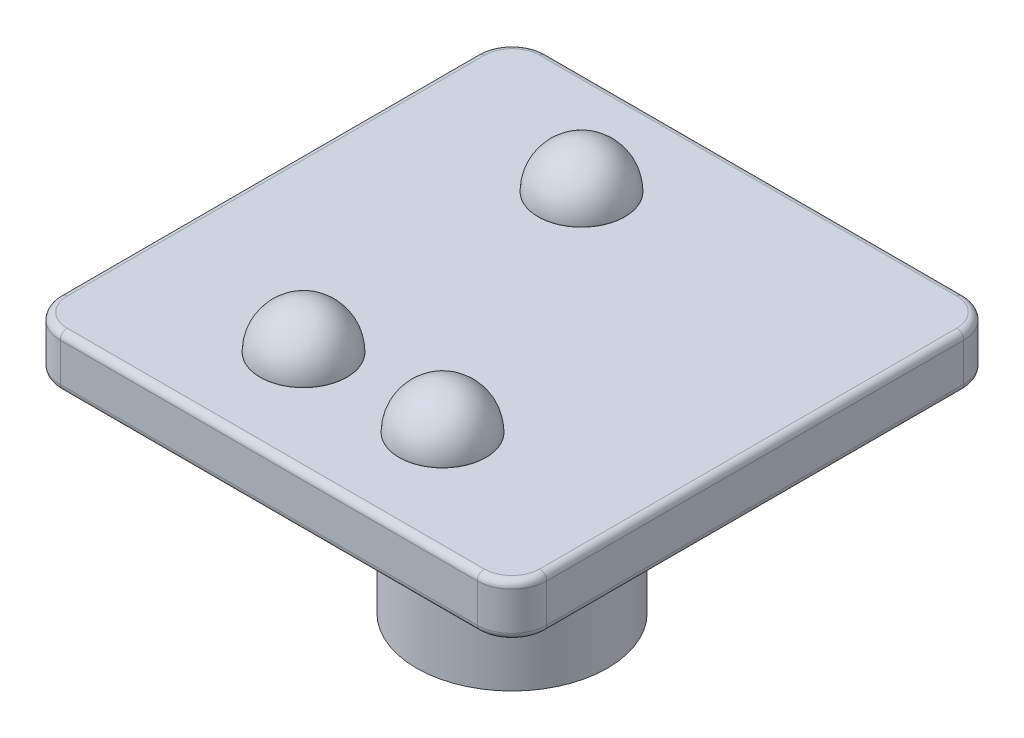
SolidWorks part; units mm, degrees
ref_plane "Front Plane" through (0, 0, 0) normal (0, 0, 1) x (1, 0, 0)
ref_plane "Top Plane" through (0, 0, 0) normal (0, 1, 0) x (1, 0, 0)
ref_plane "Right Plane" through (0, 0, 0) normal (1, 0, 0) x (0, 0, -1)
sketch "Sketch1" plane through (0, 0, 0) normal (0, 1, 0) x (1, 0, 0)
  line L1 (-7.3247, 4.3967) -> (4.6753, 4.3967)
  line L2 (-8.3247, 3.3967) -> (-8.3247, -8.6033)
  line L3 (-7.3247, -9.6033) -> (4.6753, -9.6033)
  line L4 (5.6753, 3.3967) -> (5.6753, -8.6033)
  arc A0 (-8.3247, -8.6033) -> (-7.3247, -9.6033) centre (-7.3247, -8.6033) ccw
  arc A1 (4.6753, -9.6033) -> (5.6753, -8.6033) centre (4.6753, -8.6033) ccw
  arc A2 (4.6753, 4.3967) -> (5.6753, 3.3967) centre (4.6753, 3.3967) cw
  arc A3 (-7.3247, 4.3967) -> (-8.3247, 3.3967) centre (-7.3247, 3.3967) ccw
  point P8 (5.6753, -9.6033)
  point P11 (5.6753, 4.3967)
  point P14 (-8.3247, 4.3967)
  dimension "D3" = 1
  dimension "D1" = 14
  dimension "D2" = 14
extrude "Boss-Extrude1" add sketch "Sketch1" along normal blind 1.5
sketch "Sketch2" plane through (0, 0, 0) normal (0, -1, 0) x (1, 0, 0)
  line L0 (-7.3247, 9.6033) -> (4.6753, 9.6033) construction
  line L1 (5.6753, 8.6033) -> (5.6753, -3.3967) construction
  line L2 (-1.3247, -4.3967) -> (-1.3247, 9.6033) construction
  line L3 (-8.3247, 2.6033) -> (5.6753, 2.6033) construction
  line L4 (-8.3247, -3.3967) -> (-8.3247, 8.6033) construction
  circle A0 centre (-1.3247, 2.6033) radius 2.75
  dimension "D1" = 7
  dimension "D2" = 7
extrude "Boss-Extrude2" add sketch "Sketch2" along normal blind 6
sketch "Sketch3" plane through (0, -6, 0) normal (0, -1, 0) x (1, 0, 0)
  line L0 (-1.3247, 5.3533) -> (-1.3247, -0.1467) construction
  line L1 (-3.3247, 3.1533) -> (0.6753, 3.1533)
  line L2 (-3.3247, 3.1533) -> (-3.3247, 2.0533)
  line L3 (-3.3247, 2.0533) -> (0.6753, 2.0533)
  line L4 (0.6753, 3.1533) -> (0.6753, 2.0533)
  line L5 (-1.8747, 4.6033) -> (-0.7747, 4.6033)
  line L6 (-1.8747, 4.6033) -> (-1.8747, 0.6033)
  line L7 (-1.8747, 0.6033) -> (-0.7747, 0.6033)
  line L8 (-0.7747, 4.6033) -> (-0.7747, 0.6033)
  line L9 (-4.0747, 2.6033) -> (1.4253, 2.6033) construction
  circle A3 centre (-1.3247, 2.6033) radius 2.75 construction
  circle A4 centre (-1.3247, 2.6033) radius 2.75 construction
  dimension "D7" = 0.55
  dimension "D1" = 4
  dimension "D2" = 1.1
  dimension "D3" = 1.1
  dimension "D4" = 4
  dimension "D8" = 0.55
extrude "Cut-Extrude1" cut sketch "Sketch3" against normal blind 6 contours L8 L5 L6 L1 | L1 L8 L3 L4 | L8 L1 L6 L3 | L6 L1 L2 L3 | L8 L3 L6 L7 region at (-2.5997, -6, 2.6033) region at (-1.3247, -6, 3.8783) region at (-1.3247, -6, 2.6033) region at (-0.0497, -6, 2.6033) region at (-1.3247, -6, 1.3283)
chamfer "Chamfer1" distance 0.3 angle 45 12 edges at (-1.3247, -6, 0.6033) (-1.8747, -6, 1.3283) (-2.5997, -6, 2.0533) (-3.3247, -6, 2.6033) (-2.5997, -6, 3.1533) (-0.7747, -6, 1.3283) (-0.0497, -6, 2.0533) (0.6753, -6, 2.6033) (-0.0497, -6, 3.1533) (-0.7747, -6, 3.8783) (-1.3247, -6, 4.6033) (-1.8747, -6, 3.8783)
fillet "Fillet1" radius 1 1 edges at (-1.3247, 0, -0.1467)
sketch "Sketch4" plane through (0, 1.5, 0) normal (0, 1, 0) x (1, 0, 0)
  line L0 (-1.3247, 4.3967) -> (-1.3247, -9.6033) construction
  line L1 (4.6753, 4.3967) -> (-7.3247, 4.3967) construction
  line L2 (-7.3247, -9.6033) -> (4.6753, -9.6033) construction
  line L3 (5.6753, -2.6033) -> (-8.3247, -2.6033) construction
  line L4 (-8.3247, 3.3967) -> (-8.3247, -8.6033) construction
  line L5 (5.6753, -8.6033) -> (5.6753, 3.3967) construction
  line L6 (-3.3247, 4.3967) -> (-3.3247, -9.6033) construction
  line L7 (0.6753, 4.3967) -> (0.6753, -9.6033) construction
  line L8 (-8.3247, 1.3967) -> (5.6753, 1.3967) construction
  line L9 (5.6753, -6.6033) -> (-8.3247, -6.6033) construction
  circle A0 centre (-3.3247, 1.3967) radius 1.25
  circle A3 centre (-3.3247, -6.6033) radius 1.25
  circle A4 centre (0.6753, -6.6033) radius 1.25
  dimension "D1" = 4
  dimension "D2" = 4
  dimension "D3" = 2
  dimension "D4" = 2
extrude "Boss-Extrude3" add sketch "Sketch4" along normal blind 0.01
dome "Dome1" faces to dome 1 distance 1.25 reverse direction no elliptical dome no face at (-3.3247, 1.51, -0.1467) parameters "D1"=1.25
dome "Dome5" faces to dome 1 distance 1.25 reverse direction no elliptical dome no face at (-3.3247, 1.51, 7.8533) parameters "D1"=1.25
dome "Dome6" faces to dome 1 distance 1.25 reverse direction no elliptical dome no face at (0.6753, 1.51, 7.8533) parameters "D1"=1.25
fillet "Fillet3" radius 0.2 16 edges at (5.3824, 1.5, -4.1038) (5.6753, 1.5, 2.6033) (5.3824, 1.5, 9.3104) (-1.3247, 1.5, 9.6033) (-8.0318, 1.5, 9.3104) (-8.0318, 1.5, -4.1038) (-8.3247, 1.5, 2.6033) (-1.3247, 1.5, -4.3967) (5.3824, 0, 9.3104) (5.6753, 0, 2.6033) (5.3824, 0, -4.1038) (-1.3247, 0, -4.3967) (-8.0318, 0, -4.1038) (-8.3247, 0, 2.6033) (-8.0318, 0, 9.3104) (-1.3247, 0, 9.6033)
